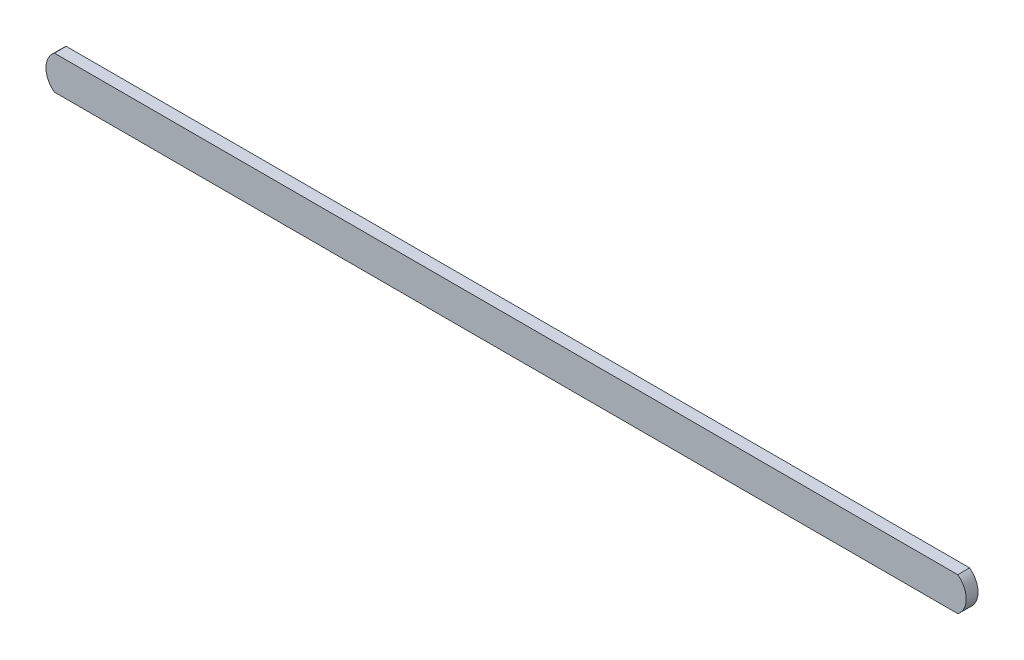
SolidWorks part; units mm, degrees
ref_plane "Front Plane" through (0, 0, 0) normal (0, 0, 1) x (1, 0, 0)
ref_plane "Top Plane" through (0, 0, 0) normal (0, 1, 0) x (1, 0, 0)
ref_plane "Right Plane" through (0, 0, 0) normal (1, 0, 0) x (0, 0, -1)
sketch "Sketch1" plane through (0, 0, 0) normal (0, 0, 1) x (1, 0, 0)
  line L1 (-52.4953, -0.507) -> (54.5047, -0.507)
  line L3 (-52.4953, -4.507) -> (54.5047, -4.507)
  arc A0 (54.5047, -0.507) -> (54.5047, -4.507) centre (53.0047, -2.507) cw
  arc A1 (-52.4953, -0.507) -> (-52.4953, -4.507) centre (-50.9953, -2.507) ccw
extrude "Boss-Extrude1" add sketch "Sketch1" along normal blind 1.4
